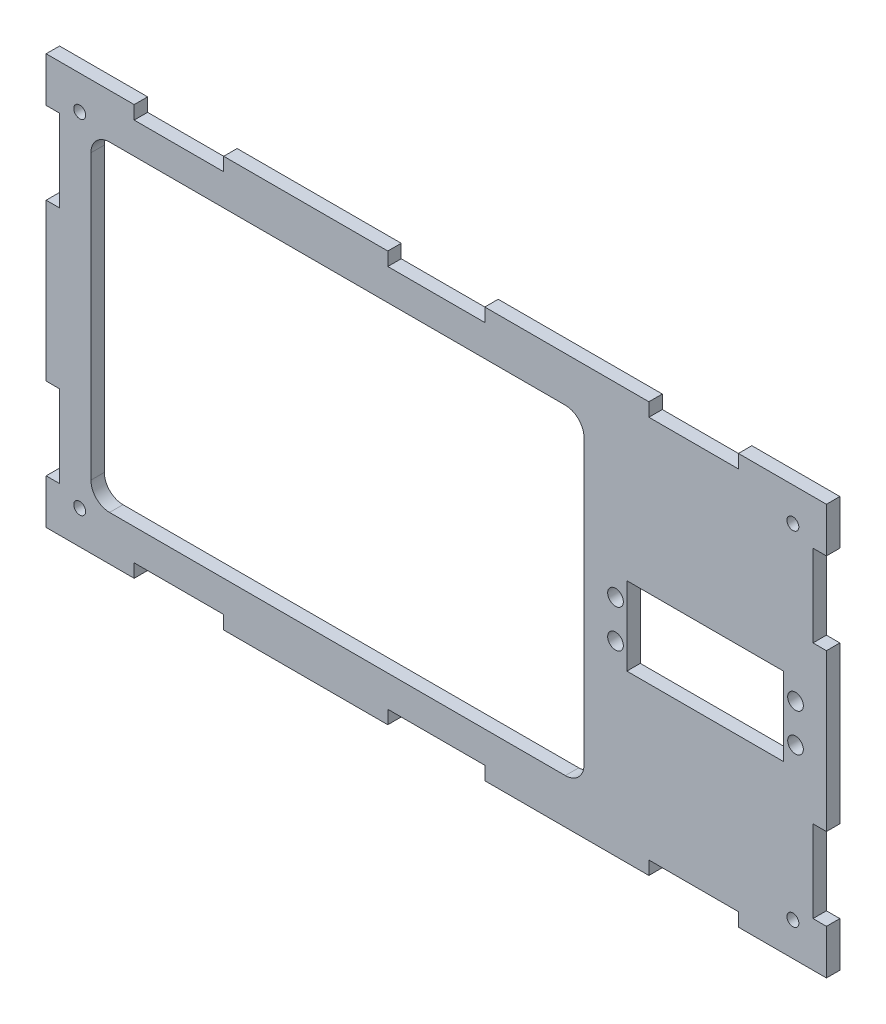
SolidWorks part; units mm, degrees
material "Бальса"
ref_plane "Спереди" through (0, 0, 0) normal (0, 0, 1) x (1, 0, 0)
ref_plane "Сверху" through (0, 0, 0) normal (0, 1, 0) x (1, 0, 0)
ref_plane "Справа" through (0, 0, 0) normal (1, 0, 0) x (0, 0, -1)
sketch "Эскиз1" plane through (0, 0, 0) normal (0, 0, 1) x (1, 0, 0)
  line L1 (0, 0) -> (209.2, 0)
  line L2 (0, 0) -> (0, 110)
  line L3 (0, 110) -> (209.2, 110)
  line L4 (209.2, 0) -> (209.2, 110)
  line L5 (17, 12) -> (139.2, 12)
  line L6 (12, 17) -> (12, 93)
  line L7 (17, 98) -> (139.2, 98)
  line L8 (144.2, 17) -> (144.2, 93)
  arc A0 (139.2, 98) -> (144.2, 93) centre (139.2, 93) cw
  arc A1 (139.2, 12) -> (144.2, 17) centre (139.2, 17) ccw
  arc A2 (17, 12) -> (12, 17) centre (17, 17) cw
  arc A3 (12, 93) -> (17, 98) centre (17, 93) cw
  dimension "D7" = 5
  dimension "D1" = 110
  dimension "D2" = 209.2
  dimension "D3" = 12
  dimension "D4" = 65
  dimension "D5" = 12
  dimension "D6" = 12
base flange "Базовая кромка1" sketch "Эскиз1" thickness 3.6 reverse thickness direction no parameters "D1"=0.7366
sketch "Эскиз6" plane through (0, 0, 0) normal (0, 0, 1) x (1, 0, 0)
  line L0 (197.7, 55) -> (209.2, 55) construction
  line L1 (155.7, 65.5) -> (197.7, 65.5)
  line L2 (155.7, 65.5) -> (155.7, 44.5)
  line L3 (155.7, 44.5) -> (197.7, 44.5)
  line L4 (197.7, 65.5) -> (197.7, 44.5)
  line L5 (209.2, 0) -> (209.2, 110) construction
  line L6 (144.2, 17) -> (144.2, 93) construction
  dimension "D1" = 21
  dimension "D2" = 42
  dimension "D3" = 11.5
extrude "Вырез-Вытянуть1" cut sketch "Эскиз6" against normal up to next normal cut yes
sketch "Эскиз7" plane through (0, 0, -3.6) normal (0, 0, -1) x (-1, 0, 0)
  line L0 (0, 110) -> (0, 0) construction
  line L1 (-3.6, 76) -> (0, 76)
  line L2 (-3.6, 76) -> (-3.6, 98)
  line L3 (-3.6, 98) -> (0, 98)
  line L4 (0, 76) -> (0, 98)
  line L5 (-209.2, 110) -> (0, 110) construction
  line L6 (-23.6, 110) -> (-47.6, 110)
  line L7 (-23.6, 110) -> (-23.6, 106.4)
  line L8 (-23.6, 106.4) -> (-47.6, 106.4)
  line L9 (-47.6, 110) -> (-47.6, 106.4)
  line L10 (-209.2, 0) -> (-209.2, 110) construction
  line L11 (-91.6, 110) -> (-117.6, 110)
  line L12 (-91.6, 110) -> (-91.6, 106.4)
  line L13 (-91.6, 106.4) -> (-117.6, 106.4)
  line L14 (-117.6, 110) -> (-117.6, 106.4)
  line L15 (-161.6, 110) -> (-185.6, 110)
  line L16 (-161.6, 110) -> (-161.6, 106.4)
  line L17 (-161.6, 106.4) -> (-185.6, 106.4)
  line L18 (-185.6, 110) -> (-185.6, 106.4)
  line L19 (-209.2, 98) -> (-205.6, 98)
  line L20 (-209.2, 98) -> (-209.2, 76)
  line L21 (-209.2, 76) -> (-205.6, 76)
  line L22 (-205.6, 98) -> (-205.6, 76)
  line L23 (0, 55) -> (-209.2, 55) construction
  line L24 (-205.6, 12) -> (-205.6, 34)
  line L25 (-209.2, 34) -> (-205.6, 34)
  line L26 (-209.2, 12) -> (-209.2, 34)
  line L27 (-209.2, 12) -> (-205.6, 12)
  line L28 (-185.6, 0) -> (-185.6, 3.6)
  line L29 (-161.6, 3.6) -> (-185.6, 3.6)
  line L30 (-161.6, 0) -> (-161.6, 3.6)
  line L31 (-161.6, 0) -> (-185.6, 0)
  line L32 (-117.6, 0) -> (-117.6, 3.6)
  line L33 (-91.6, 3.6) -> (-117.6, 3.6)
  line L34 (-91.6, 0) -> (-91.6, 3.6)
  line L35 (-91.6, 0) -> (-117.6, 0)
  line L36 (-47.6, 0) -> (-47.6, 3.6)
  line L37 (-23.6, 3.6) -> (-47.6, 3.6)
  line L38 (-23.6, 0) -> (-23.6, 3.6)
  line L39 (-23.6, 0) -> (-47.6, 0)
  line L40 (0, 34) -> (0, 12)
  line L41 (-3.6, 12) -> (0, 12)
  line L42 (-3.6, 34) -> (-3.6, 12)
  line L43 (-3.6, 34) -> (0, 34)
  dimension "D1" = 12
  dimension "D2" = 22
  dimension "D3" = 23.6
  dimension "D4" = 24
  dimension "D5" = 44
  dimension "D6" = 26
  dimension "D7" = 44
  dimension "D8" = 24
  dimension "D9" = 12
  dimension "D10" = 22
  dimension "D11" = 3.6
  dimension "D12" = 3.6
  dimension "D13" = 3.6
extrude "Вырез-Вытянуть2" cut sketch "Эскиз7" against normal up to next normal cut yes
sketch "Эскиз8" plane through (0, 0, -3.6) normal (0, 0, -1) x (-1, 0, 0)
  line L0 (-9, 9) -> (-200.2, 9) construction
  line L1 (-200.2, 9) -> (-200.2, 101) construction
  line L2 (-200.2, 101) -> (-9, 101) construction
  line L3 (-9, 101) -> (-9, 9) construction
  line L4 (0, 0) -> (-23.6, 0) construction
  line L5 (0, 76) -> (0, 34) construction
  line L6 (-23.6, 110) -> (0, 110) construction
  line L7 (-209.2, 0) -> (-209.2, 12) construction
  circle A0 centre (-200.2, 9) radius 1.6
  circle A1 centre (-9, 9) radius 1.6
  circle A2 centre (-9, 101) radius 1.6
  circle A3 centre (-200.2, 101) radius 1.6
  point P8 (0, 55)
  point P11 (-11.8, 110)
  dimension "D5" = 3.2
  dimension "D1" = 9
  dimension "D2" = 9
  dimension "D3" = 9
  dimension "D4" = 9
extrude "Вырез-Вытянуть3" cut sketch "Эскиз8" against normal blind 10 normal cut yes
sketch "Эскиз9" plane through (0, 0, -3.6) normal (0, 0, -1) x (-1, 0, 0)
  line L0 (-152.65, 60.12) -> (-152.65, 49.96) construction
  line L1 (-152.65, 49.96) -> (-200.91, 49.96) construction
  line L2 (-200.91, 49.96) -> (-200.91, 60.12) construction
  line L3 (-200.91, 60.12) -> (-152.65, 60.12) construction
  line L4 (-209.2, 34) -> (-209.2, 76) construction
  line L5 (-185.6, 0) -> (-209.2, 0) construction
  circle A0 centre (-200.91, 60.12) radius 2.1
  circle A1 centre (-200.91, 49.96) radius 2.1
  circle A2 centre (-152.65, 60.12) radius 2.1
  circle A3 centre (-152.65, 49.96) radius 2.1
  dimension "D1" = 4.2
  dimension "D2" = 10.16
  dimension "D3" = 8.29
  dimension "D4" = 49.96
  dimension "D5" = 48.26
extrude "Вырез-Вытянуть4" cut sketch "Эскиз9" against normal up to next normal cut yes
sketch "Сгиб-Линии1" plane through (0, 0, 0) normal (0, 1, 0) x (1, 0, 0)
sketch "Граничная рамка1" plane through (0, 0, 0) normal (0, 1, 0) x (1, 0, 0)
sheet metal parameters "Листовой металл4" thickness 3.6 parameters "D1"=0.7366
flat pattern "Развертка4" [suppressed]
sketch "Сгиб-Линии2" plane through (0, 0, 0) normal (0, 1, 0) x (1, 0, 0)
sketch "Граничная рамка2" [suppressed] plane through (0, 0, 0) normal (0, 1, 0) x (1, 0, 0)
sheet metal parameters "Листовой металл5" thickness 3.6 parameters "D1"=0.7366
flat pattern "Развертка4"
sketch "Сгиб-Линии2" plane through (0, 0, 0) normal (0, 1, 0) x (1, 0, 0)
sketch "Граничная рамка2" [suppressed] plane through (0, 0, 0) normal (0, 1, 0) x (1, 0, 0)
sheet metal parameters "Листовой металл6" thickness 3.6 parameters "D1"=0.7366
flat pattern "Развертка4"
sketch "Сгиб-Линии2" plane through (0, 0, 0) normal (0, 1, 0) x (1, 0, 0)
sketch "Граничная рамка2" [suppressed] plane through (0, 0, 0) normal (0, 1, 0) x (1, 0, 0)
sheet metal parameters "Листовой металл7" thickness 3.6 parameters "D1"=0.7366
flat pattern "Развертка4"
sketch "Сгиб-Линии2" plane through (0, 0, 0) normal (0, 1, 0) x (1, 0, 0)
sketch "Граничная рамка2" [suppressed] plane through (0, 0, 0) normal (0, 1, 0) x (1, 0, 0)
sheet metal parameters "Листовой металл8" thickness 3.6 parameters "D1"=0.7366
flat pattern "Развертка4"
sketch "Сгиб-Линии2" plane through (0, 0, 0) normal (0, 1, 0) x (1, 0, 0)
sketch "Граничная рамка2" [suppressed] plane through (0, 0, 0) normal (0, 1, 0) x (1, 0, 0)
